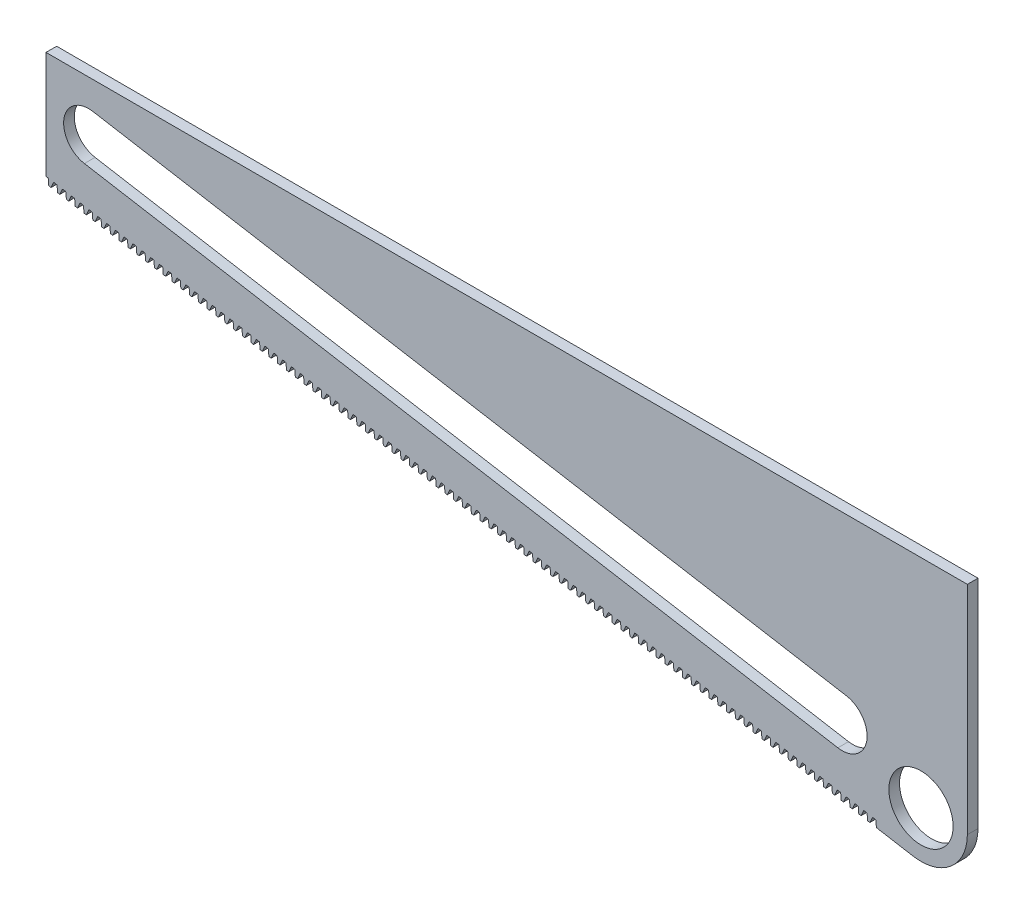
SolidWorks part; units mm, degrees
material "Polypropylene"
ref_plane "Front Plane" through (0, 0, 0) normal (0, 0, 1) x (1, 0, 0)
ref_plane "Top Plane" through (0, 0, 0) normal (0, 1, 0) x (1, 0, 0)
ref_plane "Right Plane" through (0, 0, 0) normal (1, 0, 0) x (0, 0, -1)
sketch "Sketch1" plane through (0, 0, 0) normal (0, 0, 1) x (1, 0, 0)
  line L0 (19.05, 0) -> (19.05, -76.2) construction
  line L1 (0, 19.05) -> (-57.15, 19.05) construction
  line L2 (19.05, -155.575) -> (168.9894, -155.575) construction
  line L3 (0, -95.25) -> (-57.15, -95.25) construction
  line L4 (-57.15, -95.25) -> (-57.15, 19.05) construction
  line L5 (168.9894, 7.239) -> (168.9894, -18.161) construction
  line L6 (168.9894, -18.161) -> (168.9894, -155.575) construction
  line L7 (168.9894, 7.239) -> (143.6189, 6.0141) construction
  line L8 (143.6189, 6.0141) -> (19.05, 0) construction
  line L9 (165.4887, -13.1639) -> (-221.8613, 53.2971)
  line L10 (189.6904, 7.239) -> (189.6904, 104.0971)
  line L12 (197.5644, 110.4886) -> (197.5644, -33.1911) construction
  line L13 (189.6904, 104.0971) -> (-221.8613, 104.0971)
  line L16 (-221.8613, 104.0971) -> (-221.8613, 53.2971)
  line L17 (133.7387, 22.9515) -> (-202.8113, 80.6963) construction
  line L18 (131.8487, 11.9364) -> (-204.7013, 69.6812)
  line L19 (135.6286, 33.9665) -> (-200.9214, 91.7113)
  arc A0 (19.05, 0) -> (0, 19.05) centre (0, 0) ccw construction
  arc A1 (19.05, -76.2) -> (0, -95.25) centre (0, -76.2) cw construction
  circle A2 centre (168.9894, 7.239) radius 14.351
  circle A3 centre (168.9894, 7.239) radius 25.4 construction
  arc A4 (165.4887, -13.1639) -> (189.6904, 7.239) centre (168.9894, 7.239) ccw
  arc A5 (131.8487, 11.9364) -> (135.6286, 33.9665) centre (133.7387, 22.9515) ccw
  arc A6 (-200.9214, 91.7113) -> (-204.7013, 69.6812) centre (-202.8113, 80.6963) ccw
  point P24 (-34.5363, 51.8239)
  dimension "D1" = 19.05
  dimension "D4" = 19.05
  dimension "D6" = 28.702
  dimension "D7" = 50.8
  dimension "D10" = 6.35
  dimension "D13" = 28.575
  dimension "D15" = 11.176
  dimension "D2" = 155.575
  dimension "D3" = 76.2
  dimension "D5" = 114.3
  dimension "D8" = 137.414
  dimension "D9" = 124.714
  dimension "D11" = 12.5
  dimension "D12" = 387.35
  dimension "D14" = 50.8
  dimension "D16" = 19.05
  dimension "D17" = 19.05
  dimension "D18" = 336.55
  dimension "D19" = 259.6721
extrude "Boss-Extrude1" add sketch "Sketch1" along normal blind 4.7625
sketch "Sketch2" plane through (0, 0, 4.7625) normal (0, 0, 1) x (1, 0, 0)
  line L0 (-220.6224, 53.149) -> (-220.8392, 55.7505)
  line L1 (-221.0914, 56.0256) -> (-222.1159, 56.2014)
  line L2 (-222.4453, 56.0261) -> (-223.517, 53.6456)
  line L3 (-223.5762, 53.5914) -> (-223.5719, 53.6164) construction
  line L4 (-221.6036, 56.1135) -> (-222.0804, 53.3347) construction
  line L5 (-220.5803, 54.3917) -> (-223.1424, 54.8313) construction
  line L6 (-221.8613, 53.2971) -> (165.4887, -13.1639) construction
  line L7 (-222.9946, 54.8059) -> (-223.2471, 53.3347) construction
  line L8 (-220.728, 54.417) -> (-220.9137, 53.3347) construction
  line L11 (-220.5846, 53.0781) -> (-223.5762, 53.5914)
  line L13 (-220.5803, 53.1031) -> (-220.1097, 53.0224)
  line L14 (-220.1097, 53.0224) -> (-220.114, 52.9973)
  line L15 (-220.114, 52.9973) -> (-220.5846, 53.0781)
  line L16 (-220.5846, 53.0781) -> (-220.5803, 53.1031) construction
  line L17 (-224.0425, 53.6972) -> (-224.0468, 53.6721)
  line L18 (-224.0468, 53.6721) -> (-223.5762, 53.5914)
  line L19 (-223.5719, 53.6164) -> (-224.0425, 53.6972)
  line L21 (-221.8613, 104.0971) -> (-221.8613, 53.2971) construction
  arc A0 (-222.1159, 56.2014) -> (-222.4453, 56.0261) centre (-222.1674, 55.901) ccw
  arc A1 (-220.8392, 55.7505) -> (-221.0914, 56.0256) centre (-221.1429, 55.7252) ccw
  arc A2 (-223.5719, 53.6164) -> (-223.517, 53.6456) centre (-223.5633, 53.6665) ccw
  arc A3 (-220.6224, 53.149) -> (-220.5803, 53.1031) centre (-220.5717, 53.1532) ccw
  point P6 (-221.8613, 54.6115)
  dimension "D1" = 0.0254
  dimension "Root_fillet" = 0.3048
  dimension "Break_rad" = 0.0508
  dimension "Gap_width" = 2.2997
  dimension "Dedendum" = 1.524
  dimension "Addendum_plus" = 1.2954
  dimension "Pressure_angle" = 14.5
  dimension "D2" = 0.4775
extrude "Cut-Extrude2" cut sketch "Sketch2" against normal through all
pattern_linear "LPattern2" count 95 spacing 3.9903 along (0.9856, -0.1691, 0) of "Cut-Extrude2"
